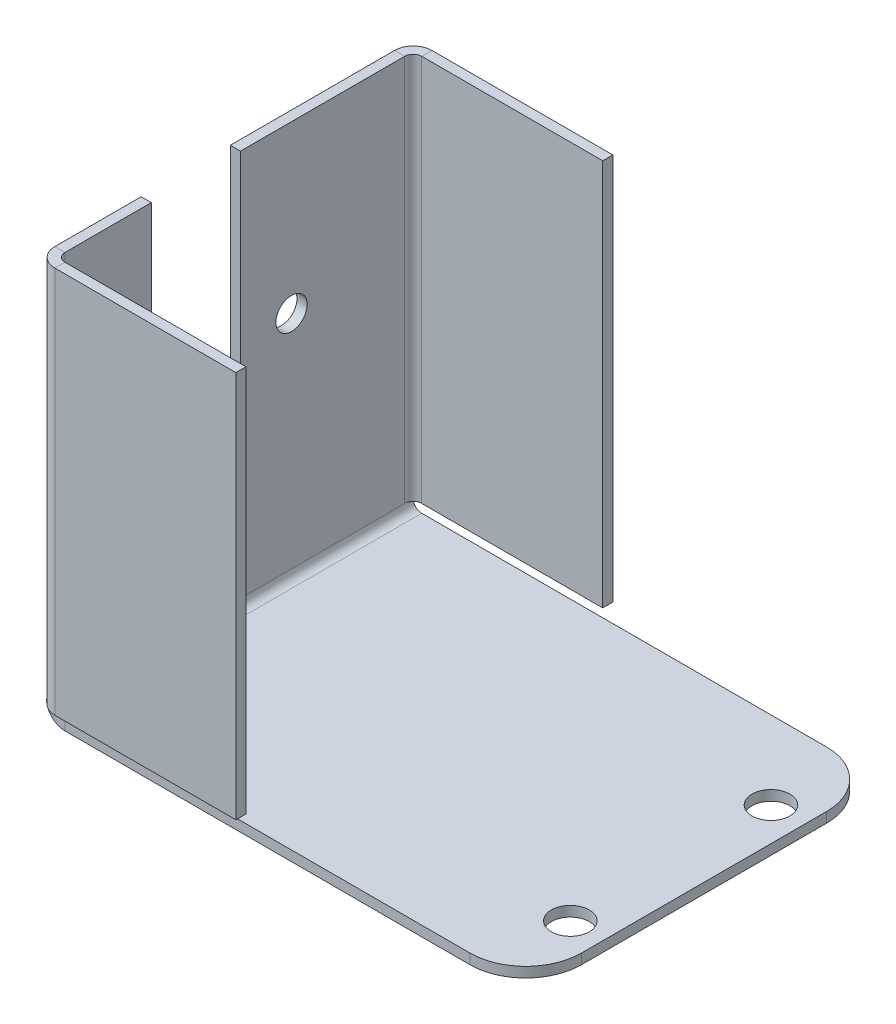
SolidWorks part; units mm, degrees
note: The reader was unsure of these and kept them because the rebuilt part matched: thickness of "Base-Flange1", "Edge-Flange1", "Edge-Flange2", "Sheet-Metal(1)", "Sheet-Metal(2)", "Sheet-Metal(3)", "Sheet-Metal(6)", "Sheet-Metal(19)", "Sheet-Metal(22)", "Sheet-Metal(24)", "Sheet-Metal(25)", "Sheet-Metal(26)"; flange length of "Edge-Flange1", "Edge-Flange2".
material "6061 Alloy"
ref_plane "Front Plane" through (0, 0, 0) normal (0, 0, 1) x (1, 0, 0)
ref_plane "Top Plane" through (0, 0, 0) normal (0, 1, 0) x (1, 0, 0)
ref_plane "Right Plane" through (0, 0, 0) normal (1, 0, 0) x (0, 0, -1)
sketch "Sketch1" plane through (0, 0, 0) normal (0, 1, 0) x (1, 0, 0)
  line L1 (0, 0) -> (43, 0)
  line L2 (0, 0) -> (0, 32)
  line L3 (0, 32) -> (43, 32)
  line L4 (43, 0) -> (43, 32)
  dimension "D1" = 43
  dimension "D2" = 32
base flange "Base-Flange1" sketch "Sketch1" thickness 0.91 reverse thickness direction no parameters "D1"=0.762
edge flange "Edge-Flange1" sketch "Sketch8" flange angle 90 flange length 35.5 flange position material inside bend radius 0.762 thickness 0.91 relief rectangular parameters "D6"=10
sketch "Sketch8" plane through (0, 0, 0) normal (-1, 0, 0) x (0, 0, 1)
  line L0 (-32, 0) -> (0, 0) construction
  line L1 (-32, 0) -> (0, 0)
  line L2 (-32, 0) -> (-32, 35.5)
  line L3 (-32, 35.5) -> (0, 35.5)
  line L4 (0, 35.5) -> (0, 0)
bend "EdgeBend1" bend radius 0.762 bend angle 90 parameters "D5"=1
sketch "Sketch9" plane through (0, 0, 0) normal (-1, 0, 0) x (0, 0, 1)
  line L1 (0, 0.762) -> (0, 35.5) construction
  line L5 (-12.5, 15) -> (-12.5, 35.8636) construction
  circle A2 centre (-12.5, 15) radius 4
  point P8 (-12.5, 15)
  dimension "D4" = 12.5
edge flange "Edge-Flange2" sketch "Sketch12" flange angle 90 flange length 17 flange position material outside bend radius 0.762 thickness 0.91 relief none parameters "D6"=10
sketch "Sketch12" plane through (0.91, 0, 0) normal (0, 0, 1) x (0, -1, 0)
  line L0 (-0.762, 0) -> (-35.5, 0) construction
  line L1 (-0.762, 0) -> (-35.5, 0)
  line L2 (-35.5, 0) -> (-35.5, 17)
  line L3 (-35.5, 17) -> (-0.762, 17)
  line L4 (-0.762, 17) -> (-0.762, 0)
bend "EdgeBend2" bend radius 0.762 bend angle 90 parameters "D5"=2
ref_plane "Plane3" through (0, 0, -16) normal (0, 0, -1) x (-1, 0, 0)
extrude "Motor Holes" cut sketch "Sketch9" against normal up to surface (0.91 mm away) normal cut yes up to face at (0.91, 18.131, -16.381)
sketch "Sketch17" plane through (0, 0, 0) normal (0, 0, 1) x (1, 0, 0)
  line L4 (43, 0) -> (43, -0.91)
sketch "Sketch26" plane through (0, 0, 0) normal (0, 0, 1) x (1, 0, 0)
  line L0 (1.672, -0.91) -> (43, -0.91) construction
  line L1 (43, 0) -> (28, 0)
  line L2 (43, 0) -> (43, -0.91)
  line L3 (43, -0.91) -> (28, -0.91)
  line L4 (28, 0) -> (28, -0.91)
  dimension "D1" = 15
mirror "Mirror4" about plane through (0, 0, -16) normal (0, 0, -1) of "Edge-Flange2"
bend "MirrorBend2" bend radius 0.762 bend angle 90 parameters "D5"=5
ref_point "Point1"
hole_wizard "M3 Clearance Hole3" positions "Sketch28" profile "Sketch27" hole size "M3" standard "ANSI Metric"
sketch "Sketch28" plane through (0, 0, 0) normal (0, 1, 0) x (1, 0, 0)
  line L0 (43, 0) -> (43, 32) construction
  line L1 (43, 32) -> (1.672, 32) construction
  line L2 (1.672, 0) -> (43, 0) construction
  line L3 (1.672, 0) -> (1.672, 32) construction
  line L6 (1.672, 0) -> (43, 0) construction
  point P0 (40, 7)
  point P2 (4.672, 3)
  point P4 (40, 25)
  dimension "D1" = 3
  dimension "D2" = 7
  dimension "D3" = 3
  dimension "D4" = 3
  dimension "D5" = 3
  dimension "D6" = 7
sketch "Sketch27" plane through (40, 0, -7) normal (1, 0, 0) x (0, 0, 1)
  line L0 (0, 0) -> (0, 13.0215)
  line L1 (0, 13.0215) -> (1.7, 12)
  line L2 (1.7, 12) -> (1.7, 0)
  line L5 (1.7, 0) -> (0, 0)
  line L10 (0, 13.0215) -> (-1.7, 12) construction
  line L11 (0, -6.35) -> (0, 107.95) construction
  dimension "Hole Dia." = 3.4
  dimension "Hole Depth" = 12
  dimension "Drill Angle" = 118
sketch "Sketch31" plane through (0, 0, 0) normal (-1, 0, 0) x (0, 0, 1)
  line L0 (-8.5, 15) -> (-16.5, 15)
  line L1 (-16.5, 15) -> (-16.5, 35.5)
  line L2 (-0.762, 35.5) -> (-31.238, 35.5) construction
  line L3 (-16.5, 35.5) -> (-8.5, 35.5)
  line L4 (-8.5, 35.5) -> (-8.5, 15)
  circle A0 centre (-12.5, 15) radius 4 construction
extrude "Cut-Extrude3" cut sketch "Sketch31" against normal blind 10 normal cut yes
fillet "Fillet2" radius 5 2 edges at (43, -0.455, 0) (43, -0.455, -32)
sketch "Sketch34" plane through (0, 0, 0) normal (-1, 0, 0) x (0, 0, 1)
  circle A0 centre (-7.1, 7.23) radius 1.4
  arc A1 (-16.5, 15) -> (-8.5, 15) centre (-12.5, 15) ccw construction
  dimension "D1" = 5.4
  dimension "D2" = 7.77
extrude "Cut-Extrude4" cut sketch "Sketch34" against normal blind 10 contours A0 normal cut yes
sketch "Sketch35" plane through (0, 0, 0) normal (-1, 0, 0) x (0, 0, 1)
  circle A0 centre (-21.08, 20.6) radius 1.4
  arc A1 (-16.5, 15) -> (-8.5, 15) centre (-12.5, 15) ccw construction
  dimension "D1" = 8.58
  dimension "D2" = 5.6
extrude "Cut-Extrude5" cut sketch "Sketch35" against normal blind 10 normal cut yes
sketch "Bend-Lines1" [suppressed] plane through (0, 0, 0) normal (0, 1, 0) x (1, 0, 0)
sketch "Bounding-Box1" [suppressed] plane through (0, 0, 0) normal (0, 1, 0) x (1, 0, 0)
sketch "Sketch20" [suppressed] plane through (0, 0, 0) normal (0, 1, 0) x (1, 0, 0)
  line L0 (42.4714, 36.2645) -> (34.4714, 36.2645) construction
  line L1 (46.672, 36.2645) -> (1.672, 36.2645) construction
  line L2 (-31.0995, 0.1355) -> (-26.0995, 0.1355)
  line L3 (42.4714, 36.0145) -> (34.4714, 36.0145)
  line L4 (42.4714, 36.5145) -> (34.4714, 36.5145)
  line L5 (27.7911, 36.2645) -> (19.7911, 36.2645) construction
  line L6 (27.7911, 36.0145) -> (19.7911, 36.0145)
  line L7 (27.7911, 36.5145) -> (19.7911, 36.5145)
  line L8 (6.543, 36.2645) -> (14.543, 36.2645) construction
  line L9 (6.543, 36.5145) -> (14.543, 36.5145)
  line L10 (6.543, 36.0145) -> (14.543, 36.0145)
  line L11 (0.7955, 21.4125) -> (0.7955, 13.4125) construction
  line L12 (0.7955, 0) -> (0.7955, 35.14) construction
  line L13 (1.0455, 21.4125) -> (1.0455, 13.4125)
  line L14 (0.5455, 21.4125) -> (0.5455, 13.4125)
  line L15 (0.7955, 32.042) -> (0.7955, 27.042) construction
  line L16 (1.0455, 32.042) -> (1.0455, 27.042)
  line L17 (0.5455, 32.042) -> (0.5455, 27.042)
  line L18 (0.7955, 8.5374) -> (0.7955, 3.5374) construction
  line L19 (1.0455, 8.5374) -> (1.0455, 3.5374)
  line L20 (0.5455, 8.5374) -> (0.5455, 3.5374)
  line L21 (-20.5603, 35.2545) -> (-14.5603, 35.2545) construction
  line L22 (0.7955, 0) -> (0.7955, 32) construction
  line L23 (-20.5603, 35.5045) -> (-14.5603, 35.5045)
  line L24 (-20.5603, 35.0045) -> (-14.5603, 35.0045)
  line L25 (-9.1822, 35.2545) -> (-4.1822, 35.2545) construction
  line L26 (-9.1822, 35.5045) -> (-4.1822, 35.5045)
  line L27 (-9.1822, 35.0045) -> (-4.1822, 35.0045)
  line L28 (-26.0995, 35.2545) -> (-31.0995, 35.2545) construction
  line L29 (-26.0995, 35.0045) -> (-31.0995, 35.0045)
  line L30 (-26.0995, 35.5045) -> (-31.0995, 35.5045)
  line L31 (-31.0995, -0.1145) -> (-26.0995, -0.1145) construction
  line L32 (-34.819, -0.1145) -> (-0.081, -0.1145) construction
  line L33 (-31.0995, -0.3645) -> (-26.0995, -0.3645)
  line L34 (-20.5603, -0.1145) -> (-14.5603, -0.1145) construction
  line L35 (-20.5603, 0.1355) -> (-14.5603, 0.1355)
  line L36 (-20.5603, -0.3645) -> (-14.5603, -0.3645)
  line L37 (-9.1822, -0.1145) -> (-4.1822, -0.1145) construction
  line L38 (-9.1822, 0.1355) -> (-4.1822, 0.1355)
  line L39 (-9.1822, -0.3645) -> (-4.1822, -0.3645)
  line L40 (6.543, -1.1245) -> (14.543, -1.1245) construction
  line L41 (1.672, -1.1245) -> (46.672, -1.1245) construction
  line L42 (6.543, -0.8745) -> (14.543, -0.8745)
  line L43 (6.543, -1.3745) -> (14.543, -1.3745)
  line L44 (19.7911, -1.1245) -> (27.7911, -1.1245) construction
  line L45 (19.7911, -0.8745) -> (27.7911, -0.8745)
  line L46 (19.7911, -1.3745) -> (27.7911, -1.3745)
  line L47 (34.4714, -1.1245) -> (42.4714, -1.1245) construction
  line L48 (34.4714, -0.8745) -> (42.4714, -0.8745)
  line L49 (34.4714, -1.3745) -> (42.4714, -1.3745)
  arc A0 (42.4714, 36.0145) -> (42.4714, 36.5145) centre (42.4714, 36.2645) ccw
  arc A1 (34.4714, 36.5145) -> (34.4714, 36.0145) centre (34.4714, 36.2645) ccw
  arc A2 (27.7911, 36.0145) -> (27.7911, 36.5145) centre (27.7911, 36.2645) ccw
  arc A3 (19.7911, 36.5145) -> (19.7911, 36.0145) centre (19.7911, 36.2645) ccw
  arc A4 (6.543, 36.5145) -> (6.543, 36.0145) centre (6.543, 36.2645) ccw
  arc A5 (14.543, 36.0145) -> (14.543, 36.5145) centre (14.543, 36.2645) ccw
  arc A6 (1.0455, 21.4125) -> (0.5455, 21.4125) centre (0.7955, 21.4125) ccw
  arc A7 (0.5455, 13.4125) -> (1.0455, 13.4125) centre (0.7955, 13.4125) ccw
  arc A8 (1.0455, 32.042) -> (0.5455, 32.042) centre (0.7955, 32.042) ccw
  arc A9 (0.5455, 27.042) -> (1.0455, 27.042) centre (0.7955, 27.042) ccw
  arc A10 (1.0455, 8.5374) -> (0.5455, 8.5374) centre (0.7955, 8.5374) ccw
  arc A11 (0.5455, 3.5374) -> (1.0455, 3.5374) centre (0.7955, 3.5374) ccw
  arc A12 (-20.5603, 35.5045) -> (-20.5603, 35.0045) centre (-20.5603, 35.2545) ccw
  arc A13 (-14.5603, 35.0045) -> (-14.5603, 35.5045) centre (-14.5603, 35.2545) ccw
  arc A14 (-9.1822, 35.5045) -> (-9.1822, 35.0045) centre (-9.1822, 35.2545) ccw
  arc A15 (-4.1822, 35.0045) -> (-4.1822, 35.5045) centre (-4.1822, 35.2545) ccw
  arc A16 (-26.0995, 35.0045) -> (-26.0995, 35.5045) centre (-26.0995, 35.2545) ccw
  arc A17 (-31.0995, 35.5045) -> (-31.0995, 35.0045) centre (-31.0995, 35.2545) ccw
  arc A18 (-31.0995, 0.1355) -> (-31.0995, -0.3645) centre (-31.0995, -0.1145) ccw
  arc A19 (-26.0995, -0.3645) -> (-26.0995, 0.1355) centre (-26.0995, -0.1145) ccw
  arc A20 (-20.5603, 0.1355) -> (-20.5603, -0.3645) centre (-20.5603, -0.1145) ccw
  arc A21 (-14.5603, -0.3645) -> (-14.5603, 0.1355) centre (-14.5603, -0.1145) ccw
  arc A22 (-9.1822, 0.1355) -> (-9.1822, -0.3645) centre (-9.1822, -0.1145) ccw
  arc A23 (-4.1822, -0.3645) -> (-4.1822, 0.1355) centre (-4.1822, -0.1145) ccw
  arc A24 (6.543, -0.8745) -> (6.543, -1.3745) centre (6.543, -1.1245) ccw
  arc A25 (14.543, -1.3745) -> (14.543, -0.8745) centre (14.543, -1.1245) ccw
  arc A26 (19.7911, -0.8745) -> (19.7911, -1.3745) centre (19.7911, -1.1245) ccw
  arc A27 (27.7911, -1.3745) -> (27.7911, -0.8745) centre (27.7911, -1.1245) ccw
  arc A28 (34.4714, -0.8745) -> (34.4714, -1.3745) centre (34.4714, -1.1245) ccw
  arc A29 (42.4714, -1.3745) -> (42.4714, -0.8745) centre (42.4714, -1.1245) ccw
  point P4 (-28.5995, -0.1145)
  point P6 (38.4714, 36.2645)
  point P11 (23.7911, 36.2645)
  point P18 (10.543, 36.2645)
  point P25 (0.7955, 17.4125)
  point P34 (0.7955, 29.542)
  point P41 (0.7955, 6.0374)
  point P48 (-17.5603, 35.2545)
  point P57 (-6.6822, 35.2545)
  point P64 (-28.5995, 35.2545)
  point P78 (-17.5603, -0.1145)
  point P85 (-6.6822, -0.1145)
  point P92 (10.543, -1.1245)
  point P101 (23.7911, -1.1245)
  point P108 (38.4714, -1.1245)
extrude "Cut-Extrude1" [suppressed] cut sketch "Sketch20" against normal up to next
sheet metal parameters "Sheet-Metal(1)" thickness 0.91 parameters "D1"=0.762
flat pattern "Flat-Pattern(1)" [suppressed]
sketch "Bend-Lines2" plane through (0, 0, 0) normal (0, 1, 0) x (1, 0, 0)
sketch "Bounding-Box2" [suppressed] plane through (0, 0, 0) normal (0, 1, 0) x (1, 0, 0)
sheet metal parameters "Sheet-Metal(2)" thickness 0.91 parameters "D1"=0.762, "D7"=0.76
flat pattern "Flat-Pattern(1)" [suppressed]
sketch "Bend-Lines2" plane through (0, 0, 0) normal (0, 1, 0) x (1, 0, 0)
sketch "Bounding-Box2" [suppressed] plane through (0, 0, 0) normal (0, 1, 0) x (1, 0, 0)
bend of the flat pattern "Flatten-<EdgeBend1>1"
sheet metal parameters "Sheet-Metal(3)" thickness 0.91 parameters "D1"=0.762, "D7"=0.76
flat pattern "Flat-Pattern(1)" [suppressed]
sketch "Bend-Lines2" plane through (0, 0, 0) normal (0, 1, 0) x (1, 0, 0)
sketch "Bounding-Box2" [suppressed] plane through (0, 0, 0) normal (0, 1, 0) x (1, 0, 0)
bend of the flat pattern "Flatten-<EdgeBend1>1"
bend of the flat pattern "Flatten-<EdgeBend2>1"
sheet metal parameters "Sheet-Metal(6)" thickness 0.91 parameters "D1"=0.762, "D7"=0.76
flat pattern "Flat-Pattern(1)" [suppressed]
sketch "Bend-Lines2" plane through (0, 0, 0) normal (0, 1, 0) x (1, 0, 0)
sketch "Bounding-Box2" [suppressed] plane through (0, 0, 0) normal (0, 1, 0) x (1, 0, 0)
bend of the flat pattern "Flatten-<EdgeBend1>1"
bend of the flat pattern "Flatten-<EdgeBend2>1"
sheet metal parameters "Sheet-Metal(19)" thickness 0.91 parameters "D1"=0.762, "D7"=0.76
flat pattern "Flat-Pattern(1)" [suppressed]
sketch "Bend-Lines2" plane through (0, 0, 0) normal (0, 1, 0) x (1, 0, 0)
sketch "Bounding-Box2" [suppressed] plane through (0, 0, 0) normal (0, 1, 0) x (1, 0, 0)
bend of the flat pattern "Flatten-<EdgeBend1>1"
bend of the flat pattern "Flatten-<EdgeBend2>1"
bend of the flat pattern "Flatten-<MirrorBend2>1"
sheet metal parameters "Sheet-Metal(22)" thickness 0.91 parameters "D1"=0.762, "D7"=0.76
flat pattern "Flat-Pattern(1)" [suppressed]
sketch "Bend-Lines2" plane through (0, 0, 0) normal (0, 1, 0) x (1, 0, 0)
sketch "Bounding-Box2" [suppressed] plane through (0, 0, 0) normal (0, 1, 0) x (1, 0, 0)
bend of the flat pattern "Flatten-<EdgeBend1>1"
bend of the flat pattern "Flatten-<EdgeBend2>1"
bend of the flat pattern "Flatten-<MirrorBend2>1"
sheet metal parameters "Sheet-Metal(24)" thickness 0.91 parameters "D1"=0.762, "D7"=0.76
flat pattern "Flat-Pattern(1)"
sketch "Bend-Lines2" plane through (0, 0, 0) normal (0, 1, 0) x (1, 0, 0)
  line L0 (-0.081, 32.1145) -> (-34.819, 32.1145) construction
  line L1 (-34.819, -0.1145) -> (-0.081, -0.1145) construction
  line L2 (0.7955, 0) -> (0.7955, 32) construction
  line L3 (-0.081, 32.1145) -> (-34.819, 32.1145) construction
  line L4 (-34.819, -0.1145) -> (-0.081, -0.1145) construction
  line L5 (0.7955, 0) -> (0.7955, 32) construction
sketch3d "Bounding-Box2" [suppressed]
  line L0 (-34.819, 49.229, 0) -> (43, 49.229, 0) construction
  line L1 (-34.819, -17.229, 0) -> (43, -17.229, 0) construction
  line L2 (-34.819, 49.229, 0) -> (-34.819, -17.229, 0) construction
  line L3 (43, 49.229, 0) -> (43, -17.229, 0) construction
bend of the flat pattern "Flatten-<EdgeBend1>1"
bend of the flat pattern "Flatten-<EdgeBend2>1"
bend of the flat pattern "Flatten-<MirrorBend2>1"
sheet metal parameters "Sheet-Metal(25)" thickness 0.91 parameters "D1"=0.762, "D7"=0.76
flat pattern "Flat-Pattern(1)"
sketch "Bend-Lines2" plane through (0, 0, 0) normal (0, 1, 0) x (1, 0, 0)
  line L0 (-0.081, 32.1145) -> (-34.819, 32.1145) construction
  line L1 (-34.819, -0.1145) -> (-0.081, -0.1145) construction
  line L2 (0.7955, 0) -> (0.7955, 32) construction
  line L3 (-0.081, 32.1145) -> (-34.819, 32.1145) construction
  line L4 (-34.819, -0.1145) -> (-0.081, -0.1145) construction
  line L5 (0.7955, 0) -> (0.7955, 32) construction
sketch3d "Bounding-Box2" [suppressed]
  line L0 (-34.819, 49.229, 0) -> (43, 49.229, 0) construction
  line L1 (-34.819, -17.229, 0) -> (43, -17.229, 0) construction
  line L2 (-34.819, 49.229, 0) -> (-34.819, -17.229, 0) construction
  line L3 (43, 49.229, 0) -> (43, -17.229, 0) construction
bend of the flat pattern "Flatten-<EdgeBend1>1"
bend of the flat pattern "Flatten-<EdgeBend2>1"
bend of the flat pattern "Flatten-<MirrorBend2>1"
sheet metal parameters "Sheet-Metal(26)" thickness 0.91 parameters "D1"=0.762, "D7"=0.76
flat pattern "Flat-Pattern(1)"
sketch "Bend-Lines2" plane through (0, 0, 0) normal (0, 1, 0) x (1, 0, 0)
  line L0 (-0.081, 32.1145) -> (-34.819, 32.1145) construction
  line L1 (-34.819, -0.1145) -> (-0.081, -0.1145) construction
  line L2 (0.7955, 0) -> (0.7955, 32) construction
  line L3 (-0.081, 32.1145) -> (-34.819, 32.1145) construction
  line L4 (-34.819, -0.1145) -> (-0.081, -0.1145) construction
  line L5 (0.7955, 0) -> (0.7955, 32) construction
sketch3d "Bounding-Box2" [suppressed]
  line L0 (-34.819, 49.229, 0) -> (43, 49.229, 0) construction
  line L1 (-34.819, -17.229, 0) -> (43, -17.229, 0) construction
  line L2 (-34.819, 49.229, 0) -> (-34.819, -17.229, 0) construction
  line L3 (43, 49.229, 0) -> (43, -17.229, 0) construction
bend of the flat pattern "Flatten-<EdgeBend1>1"
bend of the flat pattern "Flatten-<EdgeBend2>1"
bend of the flat pattern "Flatten-<MirrorBend2>1"
